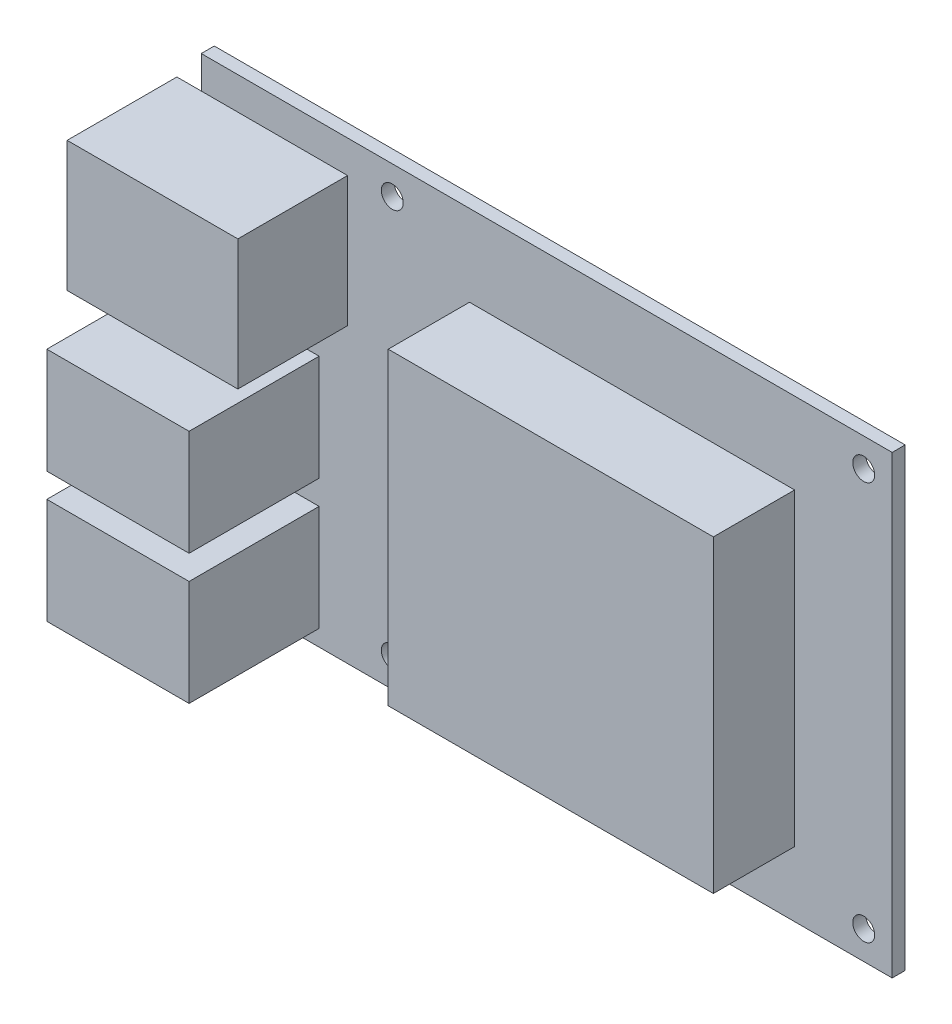
SolidWorks part; units mm, degrees
material "Cobre"
ref_plane "Alzado" through (0, 0, 0) normal (0, 0, 1) x (1, 0, 0)
ref_plane "Planta" through (0, 0, 0) normal (0, 1, 0) x (1, 0, 0)
ref_plane "Vista lateral" through (0, 0, 0) normal (1, 0, 0) x (0, 0, -1)
sketch "Sk_PCB" plane through (0, 0, 0) normal (0, 0, 1) x (1, 0, 0)
  line L1 (-95, -28) -> (-10, -28)
  line L2 (-95, -28) -> (-95, 28)
  line L3 (-95, 28) -> (-10, 28)
  line L4 (-10, -28) -> (-10, 28)
  line L5 (-95, -28) -> (-10, 28) construction
  line L6 (-95, 28) -> (-10, -28) construction
  point P0 (-52.5, 0)
  dimension "D1" = 85
  dimension "D2" = 56
  dimension "D3" = 52.5
extrude "PCB" add sketch "Sk_PCB" along normal blind 1.6 from offset 40 offset against normal yes
sketch "Sk_Barrenos_M2-5" plane through (0, 0, 0) normal (0, 0, 1) x (1, 0, 0)
  circle A0 centre (-13.5, -24.5) radius 1.35
  circle A1 centre (-13.5, 24.5) radius 1.35
  circle A2 centre (-71.5, -24.5) radius 1.35
  circle A3 centre (-71.5, 24.5) radius 1.35
  dimension "D1" = 2.7
  dimension "D4" = 2.7
  dimension "D7" = 2.7
  dimension "D10" = 2.7
  dimension "D2" = 13.5
  dimension "D3" = 24.5
  dimension "D5" = 13.5
  dimension "D6" = 24.5
  dimension "D8" = 71.5
  dimension "D9" = 24.5
  dimension "D11" = 71.5
  dimension "D12" = 24.5
extrude "Barrenos_M2-5" cut sketch "Sk_Barrenos_M2-5" along normal blind 1.6 from offset 40 offset against normal yes
sketch "Sk_Ethernet" plane through (0, 0, 0) normal (0, 0, 1) x (1, 0, 0)
  line L1 (-98, 8) -> (-77, 8)
  line L2 (-98, 8) -> (-98, 24)
  line L3 (-98, 24) -> (-77, 24)
  line L4 (-77, 8) -> (-77, 24)
  line L5 (-98, 8) -> (-77, 24) construction
  line L6 (-98, 24) -> (-77, 8) construction
  point P0 (-87.5, 16)
  dimension "D1" = 21
  dimension "D2" = 16
  dimension "D3" = 87.5
  dimension "D4" = 16
extrude "Ethernet" add sketch "Sk_Ethernet" along normal blind 13.5 from offset 38.4 offset against normal yes
sketch "Sk_USB" plane through (0, 0, 0) normal (0, 0, 1) x (1, 0, 0)
  line L1 (-98, -26) -> (-80.5, -26)
  line L2 (-98, -26) -> (-98, -13)
  line L3 (-98, -13) -> (-80.5, -13)
  line L4 (-80.5, -26) -> (-80.5, -13)
  line L5 (-98, -26) -> (-80.5, -13) construction
  line L6 (-98, -13) -> (-80.5, -26) construction
  line L7 (-98, -10) -> (-80.5, -10)
  line L8 (-98, -10) -> (-98, 3)
  line L9 (-98, 3) -> (-80.5, 3)
  line L10 (-80.5, -10) -> (-80.5, 3)
  line L11 (-98, -10) -> (-80.5, 3) construction
  line L12 (-98, 3) -> (-80.5, -10) construction
  point P0 (-89.25, -19.5)
  point P6 (-89.25, -3.5)
  dimension "D1" = 17.5
  dimension "D2" = 13
  dimension "D3" = 89.25
  dimension "D4" = 19.5
  dimension "D5" = 17.5
  dimension "D6" = 13
  dimension "D7" = 89.25
  dimension "D8" = 3.5
extrude "USB" add sketch "Sk_USB" along normal blind 16 from offset 38.4 offset against normal yes
sketch "Sk_Disipador_ventilador" plane through (0, 0, 0) normal (0, 0, 1) x (1, 0, 0)
  line L1 (-62, -20) -> (-22, -20)
  line L2 (-62, -20) -> (-62, 18)
  line L3 (-62, 18) -> (-22, 18)
  line L4 (-22, -20) -> (-22, 18)
  line L5 (-62, -20) -> (-22, 18) construction
  line L6 (-62, 18) -> (-22, -20) construction
  point P0 (-42, -1)
  dimension "D1" = 40
  dimension "D2" = 38
  dimension "D3" = 42
  dimension "D4" = 1
extrude "Disipador_ventilador" add sketch "Sk_Disipador_ventilador" along normal blind 10 from offset 38.4 offset against normal yes
